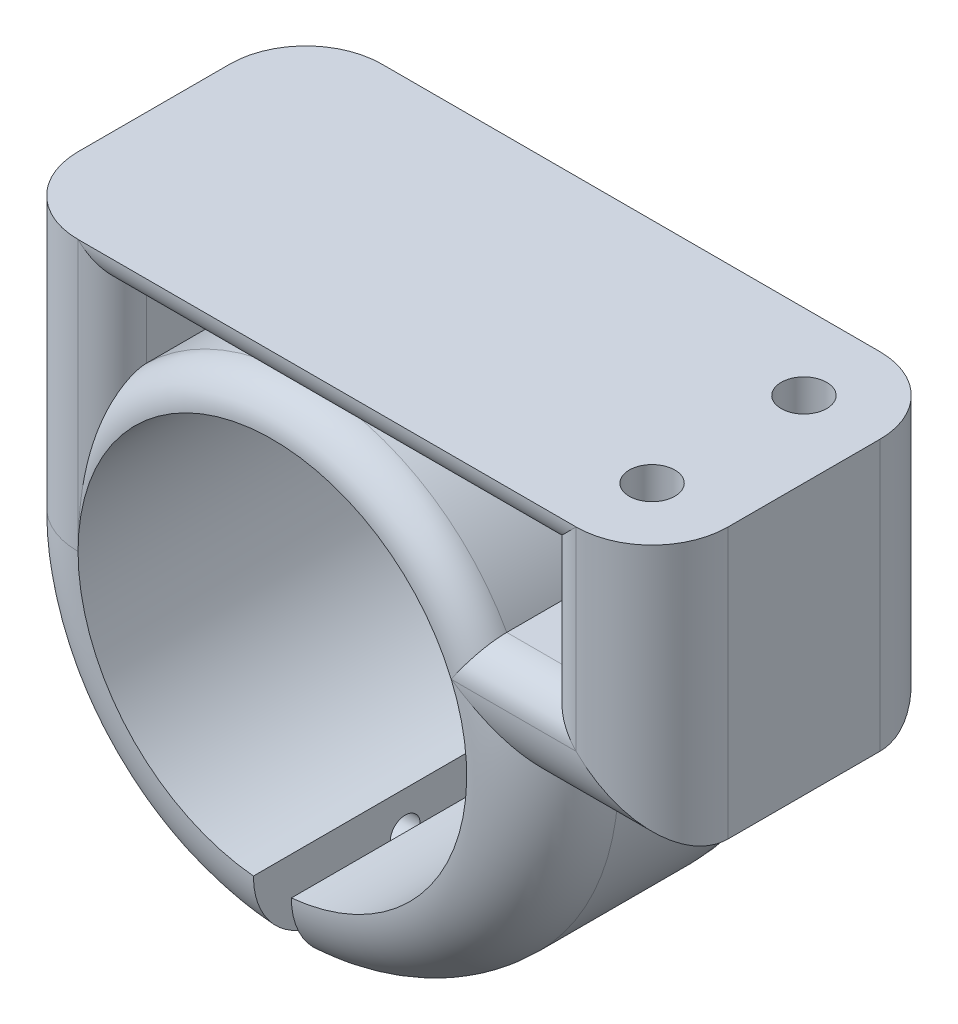
SolidWorks part; units mm, degrees
material "ABS"
ref_plane "Front Plane" through (0, 0, 0) normal (0, 0, 1) x (1, 0, 0)
ref_plane "Top Plane" through (0, 0, 0) normal (0, 1, 0) x (1, 0, 0)
ref_plane "Right Plane" through (0, 0, 0) normal (1, 0, 0) x (0, 0, -1)
sketch "Sketch2" plane through (0, 0, 0) normal (0, 1, 0) x (1, 0, 0)
  line L0 (-31.75, -12.7) -> (-31.75, 12.7) construction
  line L1 (44.45, 25.4) -> (-44.45, 25.4)
  line L2 (44.45, 25.4) -> (44.45, -25.4)
  line L3 (44.45, -25.4) -> (-44.45, -25.4)
  line L4 (-44.45, 25.4) -> (-44.45, -25.4)
  line L5 (44.45, 25.4) -> (-44.45, -25.4) construction
  line L6 (44.45, -25.4) -> (-44.45, 25.4) construction
  line L7 (-31.75, 0) -> (0, 0) construction
  line L8 (-19.05, 25.4) -> (-19.05, -25.4)
  circle A0 centre (-31.75, 12.7) radius 3.81
  circle A1 centre (-31.75, -12.7) radius 3.81
  point P0 (0, 0)
  point P1 (0, 0)
  point P7 (115.9564, 68.2319)
  dimension "D5" = 7.62
  dimension "D1" = 88.9
  dimension "D2" = 50.8
  dimension "D3" = 12.7
  dimension "D4" = 25.4
  dimension "D6" = 12.7
extrude "Boss-Extrude1" add sketch "Sketch2" against normal blind 25.4 contours L8 L1 L4 L3 A1 A0 region at (-31.75, 0, 0)
sketch "Sketch3" plane through (0, 0, 0) normal (0, 0, 1) x (1, 0, 0)
  line L0 (-31.75, 0) -> (-31.75, -12.7) construction
  line L1 (-19.05, 0) -> (-44.45, 0) construction
  line L2 (-31.75, -12.7) -> (-82.55, -12.7) construction
  line L3 (-82.55, -12.7) -> (-82.55, -45.2) construction
  line L4 (-44.45, -25.4) -> (-44.45, 0) construction
  line L5 (-44.45, 0) -> (-127.75, 0)
  line L6 (-127.75, 0) -> (-127.75, -45.2)
  line L7 (-127.75, -45.2) -> (-115.05, -45.2)
  line L8 (-19.05, -25.4) -> (-19.05, -45.2)
  line L9 (-19.05, -45.2) -> (-50.05, -45.2)
  line L10 (-19.05, -25.4) -> (-44.45, -25.4) construction
  line L11 (-44.45, -25.4) -> (-44.45, 0)
  line L12 (-19.05, -25.4) -> (-44.45, -25.4)
  circle A0 centre (-82.55, -45.2) radius 32.5
  arc A1 (-127.75, -45.2) -> (-37.35, -45.2) centre (-82.55, -45.2) ccw
  dimension "D1" = 65
  dimension "D2" = 32.5
  dimension "D3" = 12.7
  dimension "D4" = 38.1
  dimension "D5" = 12.7
extrude "Boss-Extrude2" add sketch "Sketch3" along normal mid plane 50.8 contours A0 L9 L8 L12 L11 L5 L6 L7 | L7 A1 L9 A0 region at (-45.6272, -12.7, 0) region at (-121.4, -46.2107, 0)
sketch "Sketch4" plane through (0, 0, 25.4) normal (0, 0, 1) x (1, 0, 0)
  line L0 (-82.55, -45.2) -> (-82.55, -77.7) construction
  line L2 (-85.725, -104.5667) -> (-79.375, -104.5667)
  line L3 (-85.725, -104.5667) -> (-85.725, -50.8333)
  line L4 (-85.725, -50.8333) -> (-79.375, -50.8333)
  line L5 (-79.375, -104.5667) -> (-79.375, -50.8333)
  line L6 (-85.725, -104.5667) -> (-79.375, -50.8333) construction
  line L7 (-85.725, -50.8333) -> (-79.375, -104.5667) construction
  circle A0 centre (-82.55, -45.2) radius 32.5 construction
  circle A1 centre (-82.55, -45.2) radius 32.5
  arc M4 (-127.75, -45.2) -> (-37.35, -45.2) centre (-82.55, -45.2) ccw
  circle M7 centre (-82.55, -45.2) radius 32.5
  dimension "D1" = 6.35
extrude "Cut-Extrude1" cut sketch "Sketch4" against normal blind 170.18 contours L2 L5 L3 M4 | L5 L4 L3 M7 | L5 L3 M4 M7 region at (-82.55, -97.4647, 25.4) region at (-82.55, -84.0055, 25.4) region at (-82.55, -64.2408, 25.4)
sketch "Sketch5" plane through (-127.75, 0, 0) normal (-1, 0, 0) x (0, 0, 1)
  line L0 (25.4, -77.5445) -> (-25.4, -77.5445) construction
  line L1 (25.4, -77.5445) -> (-25.4, -77.5445)
  line L2 (25.4, -77.5445) -> (25.4, -90.2884)
  line L3 (25.4, -90.2884) -> (-25.4, -90.2884) construction
  line L4 (25.4, -90.2884) -> (-25.4, -90.2884)
  line L5 (-25.4, -77.5445) -> (-25.4, -90.2884)
  line L6 (0, -90.2884) -> (0, -77.5445) construction
  line L8 (-9.525, -88.0439) -> (9.525, -88.0439)
  line L9 (-9.525, -88.0439) -> (-9.525, -79.7889)
  line L10 (-9.525, -79.7889) -> (9.525, -79.7889)
  line L11 (9.525, -88.0439) -> (9.525, -79.7889)
  line L12 (-9.525, -88.0439) -> (9.525, -79.7889) construction
  line L13 (-9.525, -79.7889) -> (9.525, -88.0439) construction
  circle A0 centre (0, -83.9164) radius 2.5
  dimension "D1" = 5
  dimension "D2" = 19.05
  dimension "D3" = 8.255
extrude "Cut-Extrude2" cut sketch "Sketch5" against normal blind 170.18 contours L6 A0 | A0 L6 region at (-127.75, -83.9164, 0)
extrude "Cut-Extrude3" cut sketch "Sketch5<3>" against normal blind 32.004 contours L8 L11 L10 L9 A0 region at (-127.75, -83.9164, -9.3174)
sketch "Sketch5<3>" plane through (-127.75, 0, 0) normal (-1, 0, 0) x (0, 0, 1) same geometry as "Sketch5"
ref_plane "Plane1" through (-82.55, 0, 0) normal (-1, 0, 0) x (0, 0, 1)
mirror "Mirror1" about plane through (-82.55, 0, 0) normal (-1, 0, 0) of "Cut-Extrude3"
sketch "Sketch6" plane through (0, -25.4, 0) normal (0, 1, 0) x (1, 0, 0)
  circle A0 centre (-31.75, -12.7) radius 3.81 construction
  circle A1 centre (-31.75, 12.7) radius 3.81 construction
  circle A2 centre (-31.75, -12.7) radius 3.81
  circle A3 centre (-31.75, 12.7) radius 3.81
extrude "Cut-Extrude4" cut sketch "Sketch6" against normal blind 32.004
fillet "Fillet1" radius 12.7 10 edges at (-115.6147, -76.0183, 25.4) (-19.05, -22.6, 25.4) (-28.2, -45.2, 25.4) (-49.4853, -76.0183, 25.4) (-127.75, -22.6, 25.4) (-127.75, -22.6, -25.4) (-115.6147, -76.0183, -25.4) (-49.4853, -76.0183, -25.4) (-28.2, -45.2, -25.4) (-19.05, -22.6, -25.4)
sketch "Sketch7" plane through (0, 0, 25.4) normal (0, 0, 1) x (1, 0, 0)
  line L4 (-49.0646, -26.785) -> (-37.465, -26.785)
  line L5 (-49.0646, -26.785) -> (-37.465, -26.785)
  line L6 (-37.465, -26.785) -> (-37.465, -5.715)
  line L7 (-37.465, -26.785) -> (-37.465, -5.715)
  line L8 (-82.55, -45.2) -> (-82.55, -5.715) construction
  line L9 (-95.25, -5.715) -> (-69.85, -5.715)
  line L14 (-37.465, -5.715) -> (-109.335, -5.715)
  line L15 (-109.335, -5.715) -> (-109.335, -17.9429)
  line L18 (-37.465, -5.715) -> (-109.335, -5.715)
  line L19 (-109.335, -5.715) -> (-109.335, -17.9429)
  arc A3 (-49.0646, -26.785) -> (-109.335, -17.9429) centre (-82.55, -45.2) ccw
  arc A4 (-49.0646, -26.785) -> (-109.335, -17.9429) centre (-82.55, -45.2) ccw
  point P3 (-82.55, -5.715)
  dimension "D1" = 5.715
extrude "Cut-Extrude6" cut sketch "Sketch7" against normal up to surface (50.8 mm away) contours A4 L18 L19 | A4 L5 L7 L18 region at (-61.1784, -12.892, 25.4) up to face at (-70.2844, -16.9405, -25.4)
fillet "Fillet2" radius 5.715 10 edges at (-43.2648, -26.785, 25.4) (-37.465, -16.25, 25.4) (-73.4, -5.715, 25.4) (-109.335, -11.8289, 25.4) (-77.003, -7.3897, 25.4) (-109.335, -11.8289, -25.4) (-73.4, -5.715, -25.4) (-37.465, -16.25, -25.4) (-43.2648, -26.785, -25.4) (-77.003, -7.3897, -25.4)
